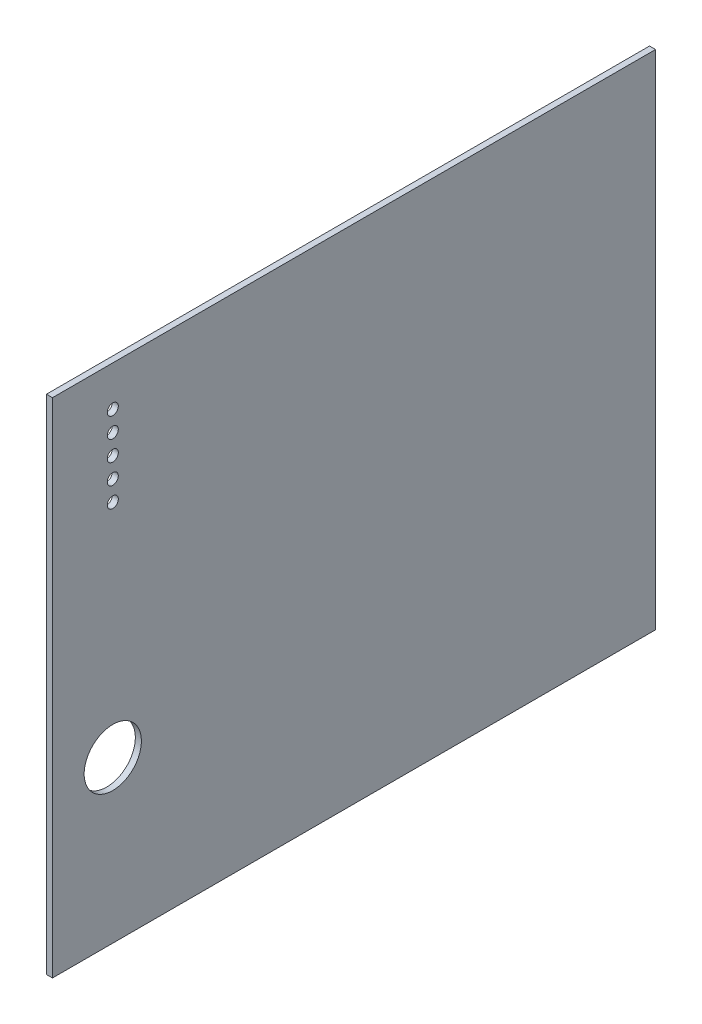
SolidWorks part; units mm, degrees
ref_plane "Front Plane" through (0, 0, 0) normal (0, 0, 1) x (1, 0, 0)
ref_plane "Top Plane" through (0, 0, 0) normal (0, 1, 0) x (1, 0, 0)
ref_plane "Right Plane" through (0, 0, 0) normal (1, 0, 0) x (0, 0, -1)
sketch "Sketch1" plane through (0, 0, 0) normal (1, 0, 0) x (0, 0, -1)
  line L1 (0, 0) -> (300, 0)
  line L2 (0, 0) -> (0, 250)
  line L3 (0, 250) -> (300, 250)
  line L4 (300, 0) -> (300, 250)
  circle A0 centre (30, 80) radius 14.235
  dimension "D1" = 300
  dimension "D5" = 28.47
  dimension "D4" = 170
  dimension "D2" = 250
  dimension "D3" = 30
extrude "Boss-Extrude1" add sketch "Sketch1" along normal blind 3
sketch "Sketch2" plane through (3, 0, 0) normal (1, 0, 0) x (0, 0, -1)
  line L0 (30, 191.2804) -> (30, 238.9618)
  line L5 (30, 238.9618) -> (249.7561, 238.9618)
  line L6 (249.7561, 238.9618) -> (249.7561, 80)
  line L7 (249.7561, 80) -> (141.2804, 80)
  arc A0 (141.2804, 80) -> (30, 191.2804) centre (30, 80) ccw
sketch "Sketch3" plane through (3, 0, 0) normal (1, 0, 0) x (0, 0, -1)
  line L0 (30, 230) -> (30, 80) construction
  circle A0 centre (30, 230) radius 2.75
  circle A1 centre (30, 220) radius 2.75
  circle A2 centre (30, 210) radius 2.75
  circle A3 centre (30, 200) radius 2.75
  circle A4 centre (30, 190) radius 2.75
  dimension "D1" = 5.5
  dimension "D3" = 10
  dimension "D2" = 150
  dimension "D4" = 10
  dimension "D5" = 10
  dimension "D6" = 10
extrude "Cut-Extrude2" cut sketch "Sketch3" against normal blind 3 contours A0 | A1 | A2 | A3 | A4
